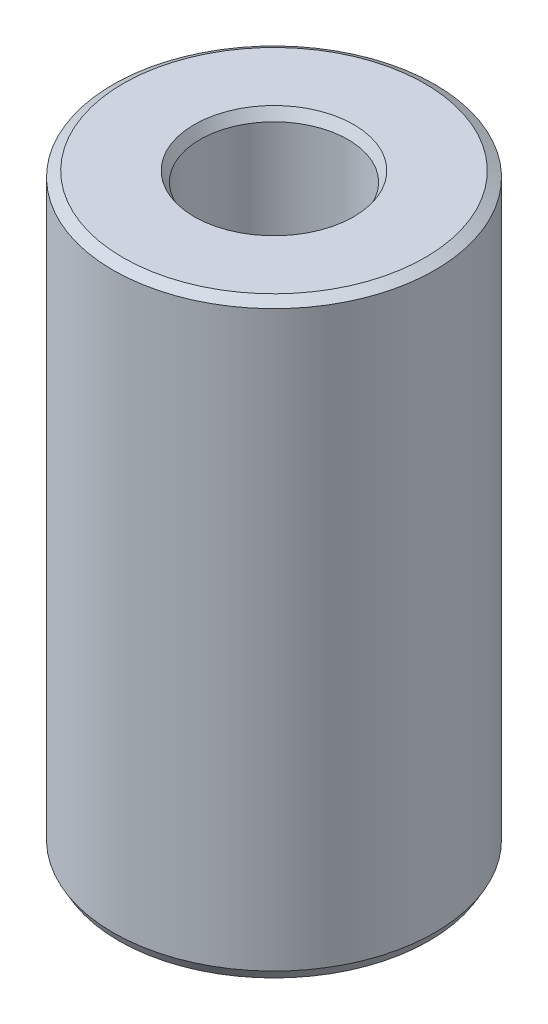
SolidWorks part; units mm, degrees
ref_plane "Front Plane" through (0, 0, 0) normal (0, 0, 1) x (1, 0, 0)
ref_plane "Top Plane" through (0, 0, 0) normal (0, 1, 0) x (1, 0, 0)
ref_plane "Right Plane" through (0, 0, 0) normal (1, 0, 0) x (0, 0, -1)
sketch "Sketch1" plane through (0, 0, 0) normal (0, 1, 0) x (1, 0, 0)
  circle A0 centre (0, 0) radius 55
  dimension "SLEEVE_OD" = 110
extrude "Boss-Extrude1" add sketch "Sketch1" along normal blind 201.5436
sketch "Sketch2" plane through (0, 0, 0) normal (0, 1, 0) x (1, 0, 0)
  circle A0 centre (0, 0) radius 25.3058
  dimension "BORE_D" = 50.6115
extrude "Cut-Extrude1" cut sketch "Sketch2" along normal through all
chamfer "Chamfer1" distance 1.9796 angle 60 4 edges at (0, 201.5436, 25.3058) (0, 0, 25.3058) (0, 0, 55) (0, 201.5436, 55) first distance on face at (0, 201.5436, 25.3058) first distance on face at (0, 0, 25.3058) first distance on face at (0, 201.5436, 55)
